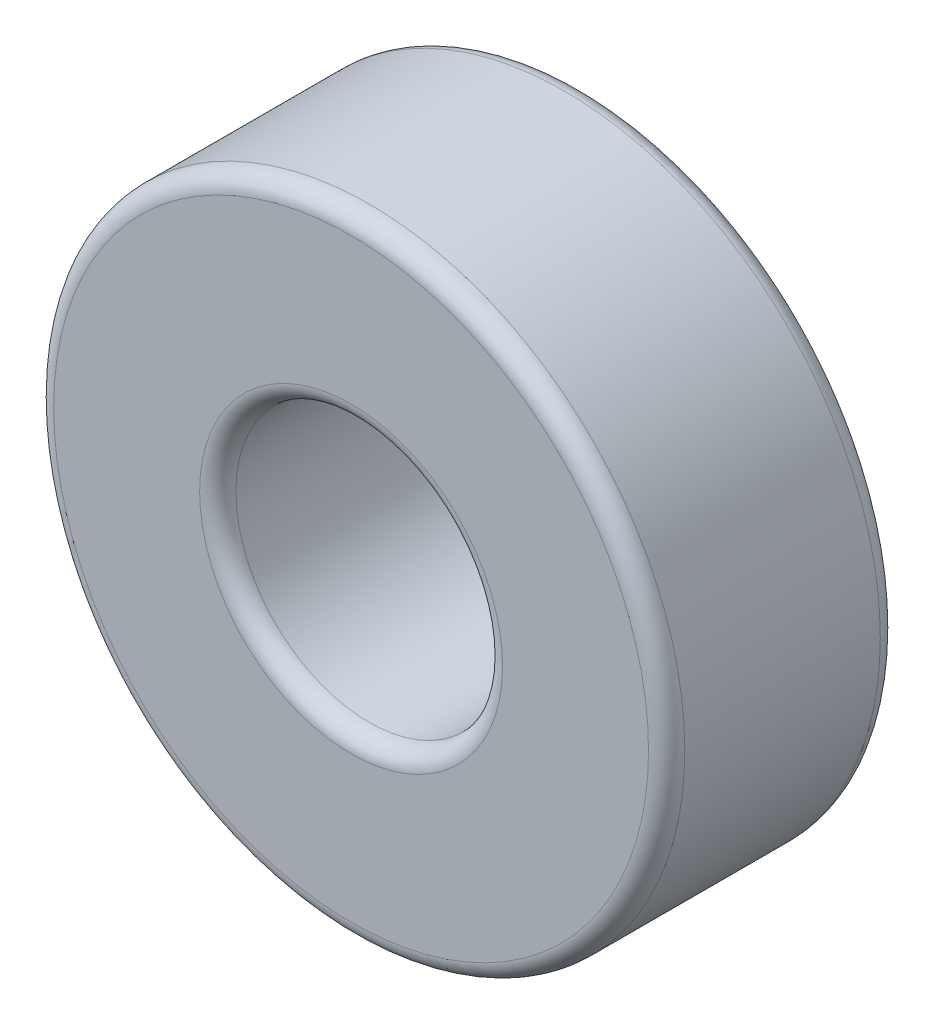
SolidWorks part; units mm, degrees
material "AISI 1020"
ref_plane "Front Plane" through (0, 0, 0) normal (0, 0, 1) x (1, 0, 0)
ref_plane "Top Plane" through (0, 0, 0) normal (0, 1, 0) x (1, 0, 0)
ref_plane "Right Plane" through (0, 0, 0) normal (1, 0, 0) x (0, 0, -1)
sketch "Sketch1" plane through (0, 0, 0) normal (0, 0, 1) x (1, 0, 0)
  circle A0 centre (0, 0) radius 9.55
  circle A1 centre (0, 0) radius 22.6
  dimension "D1" = 19.1
  dimension "D2" = 45.2
extrude "Main Extrude" add sketch "Sketch1" along normal mid plane 16.6 contours A1 A0 region at (-21.9608, 0, 0)
fillet "Fillets" radius 1.3 4 edges at (9.55, 0, -8.3) (9.55, 0, 8.3) (22.6, 0, 8.3) (22.6, 0, -8.3)
